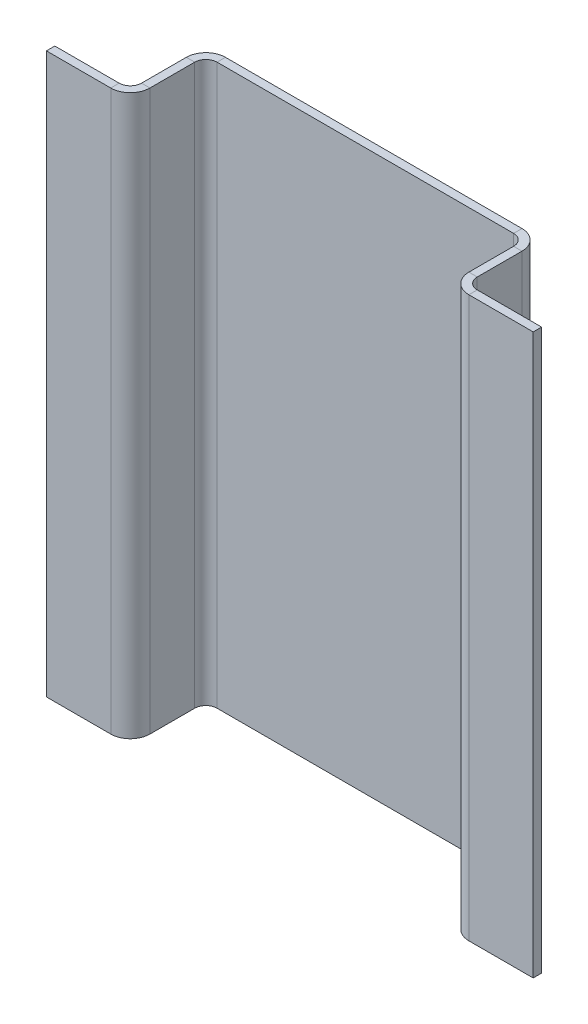
SolidWorks part; units mm, degrees
note: The reader was unsure of these and kept them because the rebuilt part matched: flange length of "边线-法兰1", "边线-法兰2".
ref_plane "前视基准面" through (0, 0, 0) normal (0, 0, 1) x (1, 0, 0)
ref_plane "上视基准面" through (0, 0, 0) normal (0, 1, 0) x (1, 0, 0)
ref_plane "右视基准面" through (0, 0, 0) normal (1, 0, 0) x (0, 0, -1)
sketch "草图1" plane through (0, 0, 0) normal (0, 0, 1) x (1, 0, 0)
  line L1 (-30, 50) -> (30, 50)
  line L2 (-30, 50) -> (-30, -50)
  line L3 (-30, -50) -> (30, -50)
  line L4 (30, 50) -> (30, -50)
  line L5 (-30, 50) -> (30, -50) construction
  line L6 (-30, -50) -> (30, 50) construction
  point P0 (0, 0)
  dimension "D1" = 60
  dimension "D2" = 100
base flange "基体-法兰1" sketch "草图1" thickness 1.5 reverse thickness direction no parameters "D1"=2
edge flange "边线-法兰1" sketch "草图10" flange profiles "草图10", "草图11" flange angle 90 flange length 15 flange position material inside bend radius 2 thickness 1.5 relief rectangular parameters "D6"=10, "D8"=1
sketch "草图10" plane through (-30, 0, 0) normal (-1, 0, 0) x (0, -1, 0)
  line L2 (-50, 0) -> (-50, 13.5)
  line L3 (-50, 13.5) -> (50, 13.5)
  line L4 (50, 13.5) -> (50, 0)
  line L5 (-50, 0) -> (50, 0) construction
  line L6 (-50, 0) -> (50, 0)
sketch "草图11" plane through (30, 0, 0) normal (1, 0, 0) x (0, 1, 0)
  line L2 (-50, 0) -> (-50, 13.5)
  line L3 (-50, 13.5) -> (50, 13.5)
  line L4 (50, 13.5) -> (50, 0)
  line L5 (-50, 0) -> (50, 0) construction
  line L6 (-50, 0) -> (50, 0)
bend "边线折弯1" bend radius 2 bend angle 90 parameters "D5"=1
bend "边线折弯2" bend radius 2 bend angle 90 parameters "D5"=2
edge flange "边线-法兰2" sketch "草图16" flange profiles "草图16", "草图17" flange angle 90 flange length 15 flange position material inside bend radius 2 thickness 1.5 relief rectangular parameters "D6"=10, "D8"=1
sketch "草图16" plane through (-30, 0, 13.5) normal (0, 0, 1) x (0, 1, 0)
  line L2 (-50, 0) -> (-50, 13.5)
  line L3 (-50, 13.5) -> (50, 13.5)
  line L4 (50, 13.5) -> (50, 0)
  line L5 (-50, 0) -> (50, 0) construction
  line L6 (-50, 0) -> (50, 0)
sketch "草图17" plane through (30, 0, 13.5) normal (0, 0, 1) x (0, -1, 0)
  line L2 (-50, 0) -> (-50, 13.5)
  line L3 (-50, 13.5) -> (50, 13.5)
  line L4 (50, 13.5) -> (50, 0)
  line L5 (-50, 0) -> (50, 0) construction
  line L6 (-50, 0) -> (50, 0)
bend "边线折弯3" bend radius 2 bend angle 90 parameters "D5"=3
bend "边线折弯4" bend radius 2 bend angle 90 parameters "D5"=4
sketch "折弯-线1" plane through (0, 0, 0) normal (0, 1, 0) x (1, 0, 0)
sketch "边界框1" plane through (0, 0, 0) normal (0, 1, 0) x (1, 0, 0)
sheet metal parameters "钣金6" thickness 1.5 parameters "D1"=2
flat pattern "平板型式6" [suppressed]
sketch "折弯-线2" plane through (0, 0, 0) normal (0, 1, 0) x (1, 0, 0)
sketch "边界框2" [suppressed] plane through (0, 0, 0) normal (0, 1, 0) x (1, 0, 0)
sheet metal parameters "钣金7" thickness 1.5 parameters "D1"=2
flat pattern "平板型式6" [suppressed]
sketch "折弯-线2" plane through (0, 0, 0) normal (0, 1, 0) x (1, 0, 0)
sketch "边界框2" [suppressed] plane through (0, 0, 0) normal (0, 1, 0) x (1, 0, 0)
bend of the flat pattern "展开-<边线折弯1>1"
bend of the flat pattern "展开-<边线折弯2>1"
sheet metal parameters "钣金8" thickness 1.5 parameters "D1"=2
flat pattern "平板型式6" [suppressed]
sketch "折弯-线2" plane through (0, 0, 0) normal (0, 1, 0) x (1, 0, 0)
sketch "边界框2" [suppressed] plane through (0, 0, 0) normal (0, 1, 0) x (1, 0, 0)
bend of the flat pattern "展开-<边线折弯1>1"
bend of the flat pattern "展开-<边线折弯2>1"
bend of the flat pattern "展开-<边线折弯3>1"
bend of the flat pattern "展开-<边线折弯4>1"
